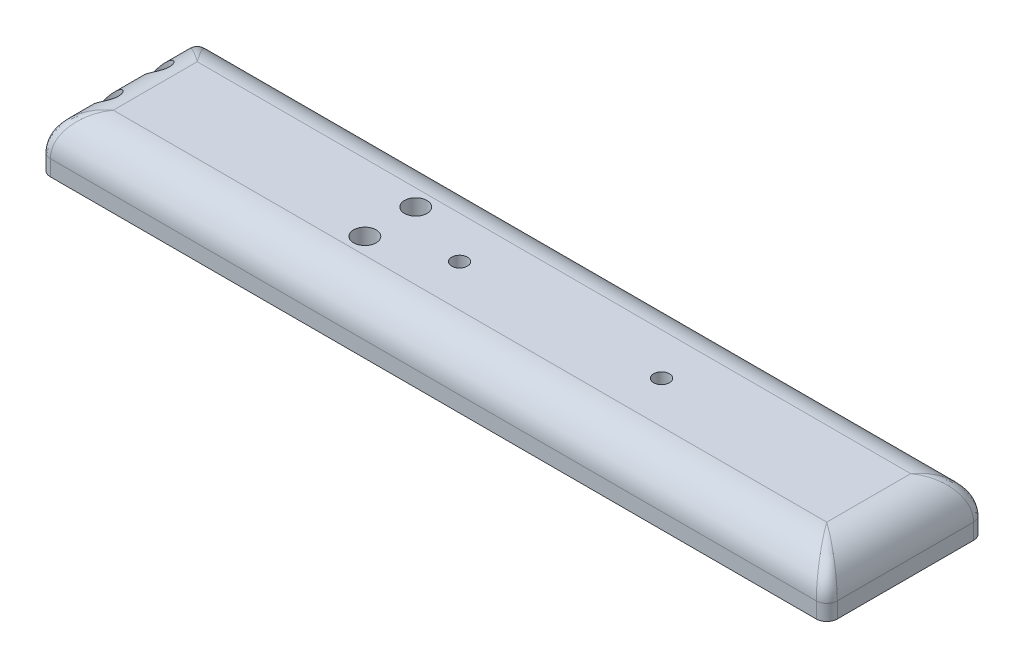
SolidWorks part; units mm, degrees
ref_plane "Front Plane" through (0, 0, 0) normal (0, 0, 1) x (1, 0, 0)
ref_plane "Top Plane" through (0, 0, 0) normal (0, 1, 0) x (1, 0, 0)
ref_plane "Right Plane" through (0, 0, 0) normal (1, 0, 0) x (0, 0, -1)
sketch "Croquis1" plane through (0, 0, 0) normal (0, 1, 0) x (1, 0, 0)
  line L0 (0, 0) -> (0, 28.483) construction
  line L1 (-75, 15) -> (75, 15)
  line L2 (-75, 15) -> (-75, -15)
  line L3 (-75, -15) -> (75, -15)
  line L4 (75, 15) -> (75, -15)
  line L5 (-75, 15) -> (75, -15) construction
  line L6 (-75, -15) -> (75, 15) construction
  circle A6 centre (-10, 0) radius 1.5
  circle A8 centre (28.5, 0) radius 1.5
  point P0 (0, 0)
  dimension "D3" = 38.5
  dimension "D5" = 3
  dimension "D1" = 30
  dimension "D2" = 150
  dimension "D6" = 10
extrude "Saliente-Extruir1" add sketch "Croquis1" along normal blind 10 contours L4 L1 L2 L3 A8 A6 | A8 | A6 region at (-0.0292, 0, 0) region at (-10, 0, 0) region at (28.5, 0, 0)
fillet "Redondeo1" radius 2 4 edges at (-75, 5, -15) (75, 5, -15) (75, 5, 15) (-75, 5, 15)
fillet "Redondeo2" radius 7 8 edges at (74.4142, 10, -14.4142) (75, 10, 0) (74.4142, 10, 14.4142) (0, 10, 15) (-74.4142, 10, 14.4142) (-75, 10, 0) (-74.4142, 10, -14.4142) (0, 10, -15)
extrude "Cortar-Extruir2" cut sketch "Croquis1<4>" along normal blind 32 contours A6 | A8
sketch "Croquis1<4>" plane through (0, 0, 0) normal (0, 1, 0) x (1, 0, 0) same geometry as "Croquis1"
sketch "Croquis3" plane through (0, 0, 0) normal (0, -1, 0) x (1, 0, 0)
  circle A0 centre (-23.2, 4.85) radius 2.15
  circle A1 centre (-23.2, -4.85) radius 2.15
  circle A2 centre (-72.3, -4.85) radius 2.15
  circle A3 centre (-72.3, 4.85) radius 2.15
  dimension "D1" = 4.3
extrude "Cortar-Extruir3" cut sketch "Croquis3" against normal blind 10
